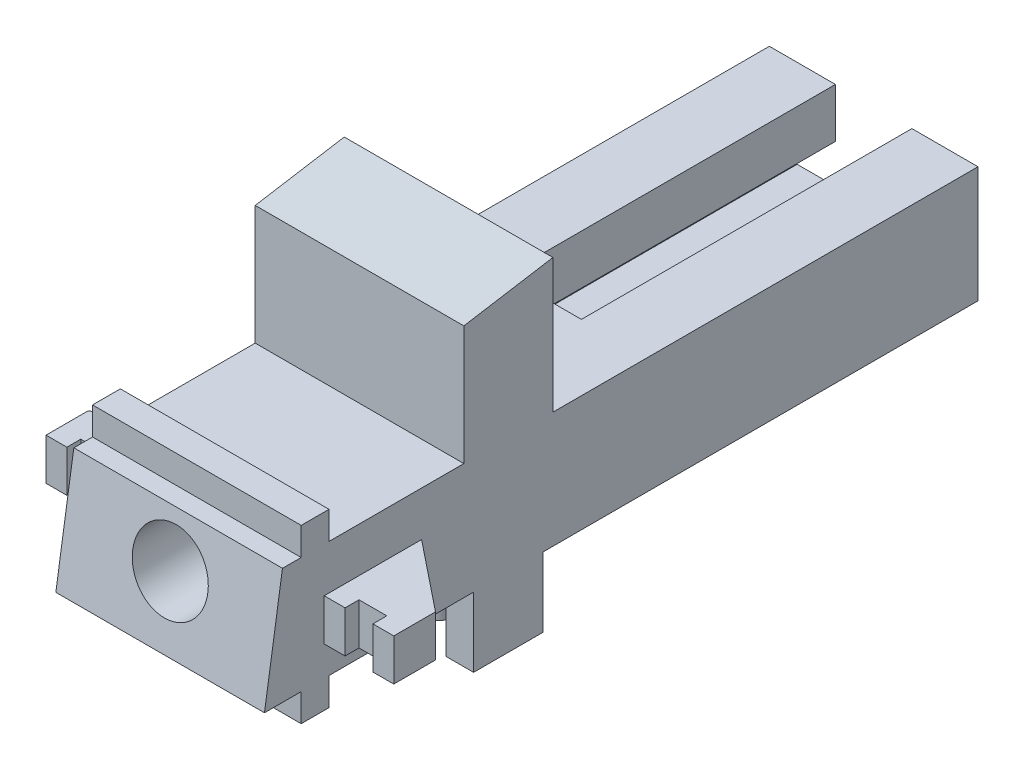
SolidWorks part; units mm, degrees
ref_plane "Front Plane" through (0, 0, 0) normal (0, 0, 1) x (1, 0, 0)
ref_plane "Top Plane" through (0, 0, 0) normal (0, 1, 0) x (1, 0, 0)
ref_plane "Right Plane" through (0, 0, 0) normal (1, 0, 0) x (0, 0, -1)
sketch "Sketch9" plane through (0, 0, 0) normal (0, 0, 1) x (1, 0, 0)
  line L1 (-7.5, 8.35) -> (7.5, 8.35)
  line L2 (-7.5, 8.35) -> (-7.5, 0)
  line L3 (-7.5, 0) -> (7.5, 0)
  line L4 (7.5, 8.35) -> (7.5, 0)
  line L5 (-7.5, 8.35) -> (7.5, 0) construction
  line L6 (-7.5, 0) -> (7.5, 8.35) construction
  point P0 (0, 4.175)
  point P19 (0, 0)
  dimension "D1" = 8.35
  dimension "D2" = 15
extrude "Boss-Extrude4" add sketch "Sketch9" along normal blind 50
sketch "Sketch7" plane through (0, 0, 0) normal (0, 0, 1) x (1, 0, 0)
  line L0 (-5.5, 2) -> (-5.5, 4.8)
  line L1 (-5.5, 4.8) -> (-2.75, 4.8)
  line L2 (-2.75, 4.8) -> (-2.75, 8.35)
  line L3 (-2.75, 8.35) -> (2.75, 8.35) construction
  line L4 (2.75, 8.35) -> (2.75, 4.8)
  line L5 (2.75, 4.8) -> (5.5, 4.8)
  line L6 (5.5, 4.8) -> (5.5, 2)
  line L7 (5.5, 2) -> (-5.5, 2)
  line L9 (7.5, 8.35) -> (-7.5, 8.35) construction
  line L11 (7.5, 0) -> (7.5, 8.35) construction
  line L13 (-2.75, 8.35) -> (2.75, 8.35)
  dimension "D1" = 2.8
  dimension "D2" = 2
  dimension "D3" = 11
  dimension "D4" = 5.5
  dimension "D5" = 2
extrude "Cut-Extrude4" cut sketch "Sketch7" along normal blind 23.76
sketch "Sketch21" plane through (-7.5, 0, 0) normal (-1, 0, 0) x (0, 0, 1)
  line L7 (50, 0) -> (51.2947, 0)
  line L8 (51.2947, 0) -> (50, 8.35)
  line L9 (50, 8.35) -> (50, 0)
extrude "Boss-Extrude9" add sketch "Sketch21" against normal up to surface (15 mm away) up to face at (7.5, 4.175, 25)
sketch "Sketch10" plane through (0, 0, 23.76) normal (0, 0, 1) x (1, 0, 0)
  line L0 (5.5, 2) -> (-5.5, 2) construction
  circle A0 centre (0, 4.7) radius 2.7
  dimension "D1" = 5.4
extrude "Cut-Extrude5" cut sketch "Sketch10" along normal up to surface (26.806 mm away) up to face at (0, 4.175, 50.6474)
sketch "Sketch12" plane through (7.5, 0, 0) normal (1, 0, 0) x (0, 0, -1)
  line L0 (-51.2947, 0) -> (0, 0) construction
  line L1 (-47, 5.14) -> (-44, 5.14)
  line L2 (-47, 5.14) -> (-47, 2.14)
  line L3 (-47, 2.14) -> (-44, 2.14)
  line L4 (-44, 5.14) -> (-44, 2.14)
  line L5 (-47, 5.14) -> (-44, 2.14) construction
  line L6 (-47, 2.14) -> (-44, 5.14) construction
  point P0 (-45.5, 3.64)
  dimension "D1" = 3
  dimension "D2" = 3
  dimension "D3" = 2.14
  dimension "D4" = 3
extrude "Boss-Extrude5" add sketch "Sketch12" along normal blind 5
ref_plane "Plane1" through (0, 0, 0) normal (1, 0, 0) x (0, 0, -1)
sketch "Sketch13" plane through (0, 0, 47) normal (0, 0, 1) x (1, 0, 0)
  line L1 (9, 5.14) -> (11, 5.14)
  line L2 (9, 5.14) -> (9, 2.14)
  line L3 (9, 2.14) -> (11, 2.14)
  line L4 (11, 5.14) -> (11, 2.14)
  line L6 (12.5, 5.14) -> (7.5, 5.14) construction
  line L7 (12.5, 2.14) -> (7.5, 2.14) construction
  point P8 (10, 5.14)
  point P9 (10, 5.14)
  dimension "D2" = 2
extrude "Cut-Extrude6" cut sketch "Sketch13" against normal blind 1
mirror "Mirror2" about plane through (0, 0, 0) normal (1, 0, 0) of "Boss-Extrude5"
mirror "Mirror4" about plane through (0, 0, 0) normal (1, 0, 0) of "Cut-Extrude6"
sketch "Sketch14" plane through (0, 5.14, 0) normal (0, 1, 0) x (1, 0, 0)
  line L0 (12.5, -44) -> (7.5, -40)
  line L1 (7.5, -50) -> (7.5, 0) construction
  line L2 (7.5, -40) -> (7.5, -44)
  line L3 (7.5, -44) -> (12.5, -44)
  dimension "D1" = 4
extrude "Boss-Extrude6" add sketch "Sketch14" against normal up to surface (3 mm away) up to face at (10, 2.14, 46)
mirror "Mirror5" about plane through (0, 0, 0) normal (1, 0, 0) of "Boss-Extrude6"
sketch "Sketch22" plane through (-7.5, 0, 0) normal (-1, 0, 0) x (0, 0, 1)
  line L0 (51.2947, 0) -> (0, 0) construction
  line L1 (48.6551, 0) -> (46.6551, 0)
  line L2 (48.6551, 0) -> (48.6551, -2)
  line L3 (48.6551, -2) -> (46.6551, -2)
  line L4 (46.6551, 0) -> (46.6551, -2)
  line L5 (48.6551, 0) -> (46.6551, -2) construction
  line L6 (48.6551, -2) -> (46.6551, 0) construction
  line L7 (50.6474, 4.175) -> (0, 4.175) construction
  line L8 (51.2947, 0) -> (50, 8.35) construction
  line L9 (0, 8.35) -> (0, 0) construction
  line L10 (48.6551, 10.35) -> (46.6551, 8.35) construction
  line L11 (48.6551, 8.35) -> (46.6551, 10.35) construction
  line L12 (46.6551, 8.35) -> (46.6551, 10.35)
  line L13 (48.6551, 10.35) -> (46.6551, 10.35)
  line L14 (48.6551, 8.35) -> (48.6551, 10.35)
  line L15 (48.6551, 8.35) -> (46.6551, 8.35)
  line L16 (50, 8.35) -> (0, 8.35) construction
  point P0 (47.6551, -1)
  point P18 (47.6551, 9.35)
  dimension "D1" = 2
extrude "Boss-Extrude10" add sketch "Sketch22" against normal up to surface (15 mm away) up to face at (7.5, 4.175, 25.3237)
sketch "Sketch23" plane through (0, 0, 0) normal (0, -1, 0) x (1, 0, 0)
  line L0 (-5.5, 23.76) -> (0, 23.76) construction
  line L2 (-7.5, 23.76) -> (7.5, 23.76) construction
  line L3 (7.5, 46.6551) -> (7.5, 0) construction
  line L4 (-7.5, 46.6551) -> (-7.5, 0) construction
  circle A0 centre (0, 29.26) radius 2.5
  dimension "D2" = 5
  dimension "D1" = 5.5
extrude "Cut-Extrude7" cut sketch "Sketch23" against normal up to surface (2 mm away) up to face at (2.7, 4.7, 23.76)
sketch "Sketch24" plane through (0, 0, 0) normal (0, -1, 0) x (1, 0, 0)
  line L0 (5.5, 36.26) -> (7.5, 36.26)
  line L1 (7.5, 46.6551) -> (7.5, 0) construction
  line L2 (7.5, 36.26) -> (7.5, 31.26)
  line L3 (7.5, 31.26) -> (5.5, 31.26)
  line L4 (5.5, 36.26) -> (-5.5, 36.26)
  line L5 (-5.5, 36.26) -> (-5.5, 31.26)
  line L6 (-5.5, 31.26) -> (5.5, 31.26)
  line L7 (5.5, 31.26) -> (5.5, 36.26)
  line L8 (5.5, 36.26) -> (-5.5, 36.26) construction
  line L9 (-5.5, 36.26) -> (-5.5, 31.26)
  line L10 (-5.5, 31.26) -> (5.5, 31.26) construction
  line L11 (5.5, 31.26) -> (5.5, 36.26)
  line L12 (-5.5, 36.26) -> (-7.5, 36.26)
  line L13 (-7.5, 46.6551) -> (-7.5, 0) construction
  line L14 (-7.5, 36.26) -> (-7.5, 31.26)
  line L15 (-7.5, 31.26) -> (-5.5, 31.26)
  line L24 (2.5, 34.76) -> (-2.5, 34.76) construction
  line L25 (2.5, 34.76) -> (-2.5, 34.76) construction
  line L26 (2.5, 32.76) -> (-2.5, 32.76) construction
  line L27 (2.5, 32.76) -> (-2.5, 32.76) construction
  line L28 (2.5, 33.01) -> (-2.5, 33.01)
  line L29 (2.5, 34.51) -> (-2.5, 34.51)
  line L34 (0, 0) -> (0, 51.2947) construction
  line L35 (-7.5, 0) -> (7.5, 0) construction
  line L36 (7.5, 51.2947) -> (-7.5, 51.2947) construction
  arc A0 (2.5, 32.76) -> (2.5, 34.76) centre (2.5, 33.76) ccw construction
  arc A1 (2.5, 32.76) -> (2.5, 34.76) centre (2.5, 33.76) ccw construction
  arc A2 (-2.5, 34.76) -> (-2.5, 32.76) centre (-2.5, 33.76) ccw construction
  arc A3 (-2.5, 34.76) -> (-2.5, 32.76) centre (-2.5, 33.76) ccw construction
  arc A4 (-2.5, 34.51) -> (-2.5, 33.01) centre (-2.5, 33.76) ccw
  arc A5 (2.5, 33.01) -> (2.5, 34.51) centre (2.5, 33.76) ccw
  dimension "D1" = 0
  dimension "D2" = 0.25
extrude "Boss-Extrude11" add sketch "Sketch24" along normal blind 5
sketch "Sketch25" plane through (7.5, 0, 0) normal (1, 0, 0) x (0, 0, -1)
  line L0 (-31.26, -5) -> (-36.26, -5) construction
  line L1 (-30.5589, 8.35) -> (-36.9611, 8.35)
  line L2 (-30.5589, 8.35) -> (-30.5589, 17.9804)
  line L4 (-36.9611, 8.35) -> (-36.9611, 16.9226)
  line L7 (-46.6551, 8.35) -> (0, 8.35) construction
  line L9 (-48.9787, 14.9368) -> (-26.8966, 18.5855) construction
  line L10 (-36.9611, 16.9226) -> (-30.5589, 17.9804)
  point P7 (-33.76, -5)
  point P8 (-33.76, 8.35)
extrude "Boss-Extrude12" add sketch "Sketch25" against normal up to surface (15 mm away) up to face at (-7.5, 2.5063, 38.5984)
